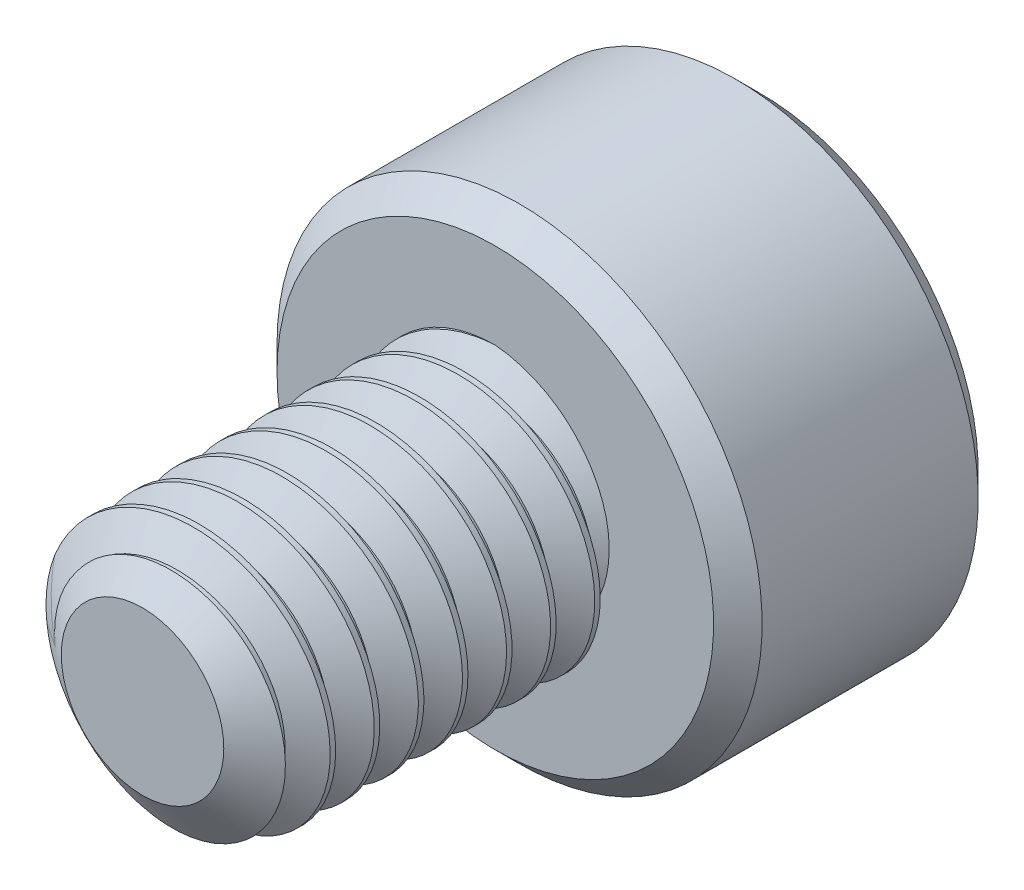
SolidWorks part; units mm, degrees
other "DetailItem1"
ref_plane "Front Plane" through (0, 0, 0) normal (0, 0, 1) x (1, 0, 0)
ref_plane "Top Plane" through (0, 0, 0) normal (0, 1, 0) x (1, 0, 0)
ref_plane "Right Plane" through (0, 0, 0) normal (1, 0, 0) x (0, 0, -1)
sketch "Sketch1" plane through (0, 0, 0) normal (0, 0, 1) x (1, 0, 0)
  circle A0 centre (0, 0) radius 1.5
  dimension "OD" = 3
extrude "Extrude1" add sketch "Sketch1" against normal blind 4
sketch "Sketch2" plane through (0, 0, 0) normal (0, 0, 1) x (1, 0, 0)
  circle A0 centre (0, 0) radius 1.5 construction
  circle A1 centre (0, 0) radius 1.5
curve "Helix/Spiral1" pitch 0.5 height 4.5 radius 1.5 centre (0, 0, 0) axis (0, 0, -1) start towards (0, 1, 0) parameters "pitch"=0.5
sketch "Sketch3" plane through (0, 0, 0) normal (1, 0, 0) x (0, 0, -1)
  line L0 (-0.4375, 1.5) -> (-0.25, 1.1752)
  line L1 (-0.25, 1.1752) -> (-0.1875, 1.1752)
  line L2 (-0.1875, 1.1752) -> (0, 1.5)
  line L3 (-0.4375, 1.5) -> (0, 1.5)
  line L4 (-0.2187, 1.5) -> (-0.2188, 1.1752) construction
  line L5 (-0.3438, 1.3376) -> (-0.0938, 1.3376) construction
  line L6 (0, 1.5) -> (0, -1.5) construction
  dimension "D1" = 0.0625
  dimension "D2" = 0.25
  dimension "D3" = 60
sweep "Cut-Sweep1" cut profiles "Sketch3" path "Helix/Spiral1"
sketch "Sketch4" plane through (0, 0, 0) normal (1, 0, 0) x (0, 0, -1)
  line L0 (0.4053, 1.5) -> (0, 0.9212)
  line L1 (0, 0.9212) -> (0, 1.5)
  line L2 (0.4053, 1.5) -> (0, 1.5)
  line L3 (-0.4375, 1.5) -> (0, 1.5) construction
  line L4 (0, 0) -> (7.0209, 0) construction
  dimension "D1" = 55
  dimension "D2" = 0.254
revolve "Cut-Revolve1" cut sketch "Sketch4" angle 360 about L4
sketch "Sketch6" plane through (0, 0, -4) normal (0, 0, -1) x (-1, 0, 0)
  circle A0 centre (0, 0) radius 2.75
  dimension "head dia" = 5.5
extrude "Extrude2" add sketch "Sketch6" along normal blind 3
sketch "Sketch7" plane through (0, 0, -7) normal (0, 0, -1) x (-1, 0, 0)
  line L1 (0, 1.4434) -> (-1.25, 0.7217)
  line L2 (-1.25, 0.7217) -> (-1.25, -0.7217)
  line L3 (-1.25, -0.7217) -> (0, -1.4434)
  line L4 (0, -1.4434) -> (1.25, -0.7217)
  line L5 (1.25, -0.7217) -> (1.25, 0.7217)
  line L6 (1.25, 0.7217) -> (0, 1.4434)
  circle A0 centre (0, 0) radius 1.25 construction
  dimension "hex dia" = 2.5
extrude "Cut-Extrude1" cut sketch "Sketch7" against normal blind 1.875
sketch "Sketch8" plane through (0, 0, -7) normal (0, 0, -1) x (-1, 0, 0)
  circle A0 centre (0, 0) radius 1.4434
extrude "Cut-Extrude2" cut sketch "Sketch8" against normal through all draft 45
chamfer "Chamfer1" distance 0.275 angle 45 2 edges at (-2.75, 0, -7) (-2.75, 0, -4)
sketch "Sketch10" plane through (0, 0, -4) normal (0, 0, 1) x (1, 0, 0)
  circle A1 centre (0, 0) radius 1.5
  circle A2 centre (0, 0) radius 1.5
  dimension "D1" = 0
ref_plane "Plane1" through (0, 0, 0) normal (0, 0, 1) x (1, 0, 0)
extrude "partial thread" [suppressed] add sketch "Sketch10" along normal up to surface (4 mm away) separate body up to plane "Plane1"
chamfer "Chamfer2" [suppressed] distance 0.06 angle 45
combine bodies "Combine1" [suppressed] operation type add bodies to combine 107 108
sketch "Sketch9" plane through (0, 0, 0) normal (1, 0, 0) x (0, 0, -1)
  line L0 (0, 1.5) -> (0, -1.5) construction
  line L1 (1.25, 1.5) -> (1.25, -1.5) construction
  dimension "D1" = 1.25
  dimension "D4" = 0.635
  dimension "D5" = 0.3302
equation "\"D3@Helix/Spiral1\" = \"screw length@Extrude1\"+\"pitch@Helix/Spiral1\""
equation "\"D1@Sketch3\" = \"pitch@Helix/Spiral1\"*.125"
equation "\"D2@Sketch3\" = \"pitch@Helix/Spiral1\"*.5"
equation "\"D1@Cut-Extrude1\" = \"hex dia@Sketch7\"*.75"
equation "\"D1@Chamfer1\" = \"head dia@Sketch6\"*.05"
equation "\"D1@Sketch9\" = \"pitch@Helix/Spiral1\"*2.5"
equation "\"D1@Chamfer2\"=\"OD@Sketch1\"*.02"
